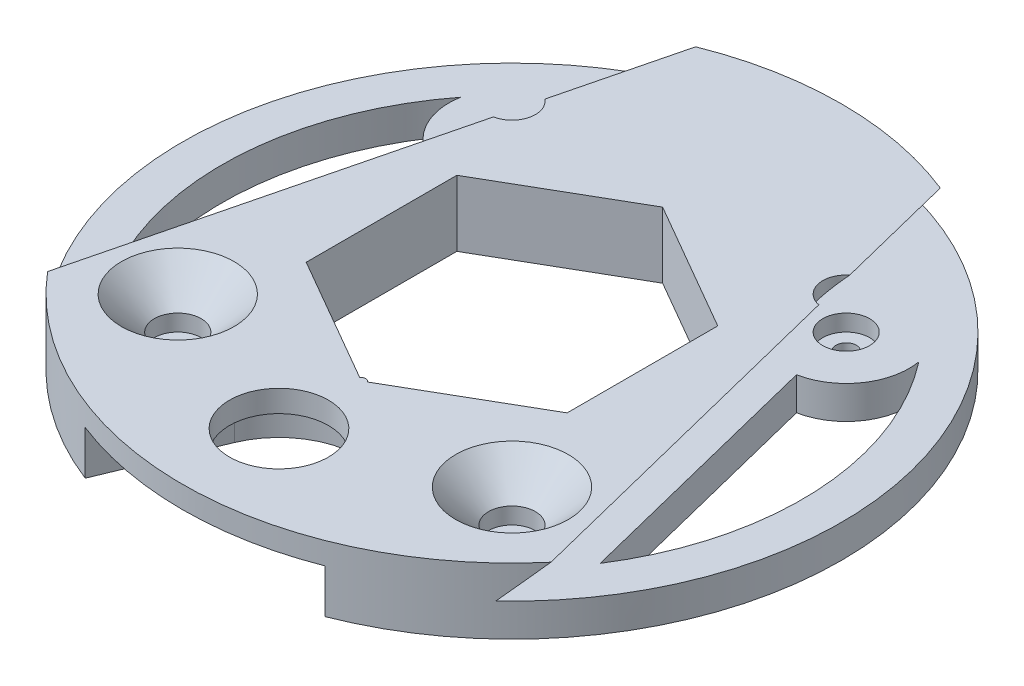
SolidWorks part; units mm, degrees
note: The reader was unsure of these and kept them because the rebuilt part matched: shared geometry of "Sketch1<6>", "Sketch5<3>".
ref_plane "Front Plane" through (0, 0, 0) normal (0, 0, 1) x (1, 0, 0)
ref_plane "Top Plane" through (0, 0, 0) normal (0, 1, 0) x (1, 0, 0)
ref_plane "Right Plane" through (0, 0, 0) normal (1, 0, 0) x (0, 0, -1)
sketch "Sketch1" plane through (0, 0, 0) normal (0, 1, 0) x (1, 0, 0)
  line L0 (-35.3553, -35.3553) -> (-12.941, 48.2963) construction
  line L1 (-34.1053, -36.5626) -> (34.1053, -36.5626) construction
  line L2 (-34.1053, -36.5626) -> (-34.1053, 36.5626) construction
  line L3 (-34.1053, 36.5626) -> (34.1053, 36.5626) construction
  line L4 (34.1053, -36.5626) -> (34.1053, 36.5626) construction
  line L5 (-34.1053, -36.5626) -> (34.1053, 36.5626) construction
  line L6 (-34.1053, 36.5626) -> (34.1053, -36.5626) construction
  line L7 (0, 96.5926) -> (0, -94.4212) construction
  line L8 (-34.1053, -36.5626) -> (-11.2548, 48.7168) construction
  line L9 (-35.3553, -35.3553) -> (35.3553, -35.3553) construction
  line L10 (-34.1053, -36.5626) -> (-12.941, 48.2963)
  line L11 (34.1053, -36.5626) -> (12.941, 48.2963)
  circle A0 centre (0, 0) radius 50
  dimension "D1" = 100
  dimension "D4" = 70.7107
  dimension "D2" = 15
  dimension "D3" = 68.2107
  dimension "D5" = 15
extrude "Boss-Extrude1" add sketch "Sketch1" against normal blind 5 contours A0
extrude "Boss-Extrude3" add sketch "Sketch1<6>" along normal blind 5
sketch "Sketch1<6>" plane through (0, 0, 0) normal (0, 1, 0) x (1, 0, 0) same geometry as "Sketch1"
draft "Draft2" type of draft neutral plane draft angle 45 faces to draft 2 face at (23.5231, 2.5, -5.8668) face at (-23.5231, 2.5, -5.8668) neutral plane through (0, 0, 0) neutral plane normal (0, 1, 0) reverse direction yes parameters "D1"=45
sketch "Sketch3" plane through (0, -5, 0) normal (0, -1, 0) x (1, 0, 0)
  line L1 (-35.3553, -35.3553) -> (35.3553, -35.3553) construction
  line L2 (-35.3553, -35.3553) -> (-35.3553, 35.3553) construction
  line L3 (-35.3553, 35.3553) -> (35.3553, 35.3553) construction
  line L4 (35.3553, -35.3553) -> (35.3553, 35.3553) construction
  line L5 (-35.3553, -35.3553) -> (35.3553, 35.3553) construction
  line L6 (-35.3553, 35.3553) -> (35.3553, -35.3553) construction
  circle A0 centre (0, 0) radius 50 construction
  circle A2 centre (0, 35.3553) radius 7.5
  point P0 (0, 0)
  dimension "D1" = 15
extrude "Cut-Extrude3" cut sketch "Sketch3" against normal through all both
sketch "Sketch4" plane through (0, -5, 0) normal (0, -1, 0) x (1, 0, 0)
  line L0 (0, 2.6913) -> (23.313, 58.9739)
  line L1 (-23.313, 58.9739) -> (0, 2.6913)
  line L2 (0, 25.3553) -> (0, 59.4863) construction
  circle A1 centre (0, 0) radius 50
  circle A2 centre (0, 0) radius 50
  circle A6 centre (0, 35.3553) radius 12.5
  circle A7 centre (0, 35.3553) radius 12.5
  circle M5 centre (0, 35.3553) radius 7.5
  circle M6 centre (0, 0) radius 50
  dimension "D2" = 5
  dimension "D3" = 45
  dimension "D1" = 0
extrude "Cut-Extrude5" cut sketch "Sketch4" against normal blind 6.6667 contours L2 A7 M5 | A7 L2 M5 | L2 A7 L0 M6 | A7 L2 A2 L1
sketch "Sketch5" plane through (0, -5, 0) normal (0, -1, 0) x (1, 0, 0)
  line L0 (-25.3553, 25.3553) -> (25.3553, 25.3553) construction
  line L1 (-35.3553, -35.3553) -> (35.3553, -35.3553) construction
  line L2 (-35.3553, -35.3553) -> (-35.3553, 35.3553) construction
  line L3 (-35.3553, 35.3553) -> (35.3553, 35.3553) construction
  line L4 (35.3553, -35.3553) -> (35.3553, 35.3553) construction
  line L5 (-35.3553, -35.3553) -> (35.3553, 35.3553) construction
  line L6 (-35.3553, 35.3553) -> (35.3553, -35.3553) construction
  line L7 (25.3553, -25.3553) -> (25.3553, 25.3553) construction
  line L8 (-25.3553, -25.3553) -> (25.3553, -25.3553) construction
  line L9 (-25.3553, -25.3553) -> (-25.3553, 25.3553) construction
  line L12 (0, -5.5) -> (0, 5.5) construction
  line L13 (5.5, 0) -> (-5.5, 0) construction
  arc A0 (-18.1786, 46.5783) -> (18.1786, 46.5783) centre (0, 0) ccw construction
  circle A1 centre (-25.3553, 25.3553) radius 1.55
  circle A4 centre (-25.3553, 25.3553) radius 3.55
  circle A5 centre (25.3553, 25.3553) radius 1.55
  circle A6 centre (25.3553, 25.3553) radius 3.55
  circle A7 centre (25.3553, -25.3553) radius 1.55
  circle A8 centre (25.3553, -25.3553) radius 3.55
  circle A9 centre (-25.3553, -25.3553) radius 1.55
  circle A10 centre (-25.3553, -25.3553) radius 3.55
  point P0 (0, 0)
  dimension "D3" = 3.1
  dimension "D2" = 10
  dimension "D1" = 10
  dimension "D4" = 2
extrude "Cut-Extrude6" cut sketch "Sketch5" against normal through all contours A6 A5 | A5 | A8 A7 | A7 | A9 | A10 A9 | A4 A1 | A1
extrude "Boss-Extrude4" add sketch "Sketch5<3>" against normal blind 2.5 contours A8 A7 | A10 A9 | A6 A5 | A4 A1
sketch "Sketch5<3>" plane through (0, -5, 0) normal (0, -1, 0) x (1, 0, 0) same geometry as "Sketch5"
sketch "Sketch6" plane through (0, 5, 0) normal (0, 1, 0) x (1, 0, 0)
  line L1 (0, -22.8553) -> (19.7933, -11.4277)
  line L2 (19.7933, -11.4277) -> (19.7933, 11.4277)
  line L3 (19.7933, 11.4277) -> (0, 22.8553)
  line L4 (0, 22.8553) -> (-19.7933, 11.4277)
  line L5 (-19.7933, 11.4277) -> (-19.7933, -11.4277)
  line L6 (-19.7933, -11.4277) -> (0, -22.8553)
  arc A0 (11.5485, -30.5718) -> (-11.5485, -30.5718) centre (0, -35.3553) ccw construction
  arc A1 (11.5485, -30.5718) -> (-11.5485, -30.5718) centre (0, -35.3553) ccw
  circle A2 centre (0, 0) radius 19.7933 construction
  circle A3 centre (0, -22.8553) radius 0.6639
extrude "Cut-Extrude8" cut sketch "Sketch6" against normal through all contours A3 L1 L2 L3 L4 L5 L6
chamfer "Chamfer1" distance 5 angle 45 2 edges at (25.3553, 5, 21.8053) (-25.3553, 5, 21.8053)
sketch "Sketch7" plane through (0, 0, 0) normal (0, 1, 0) x (1, 0, 0)
  line L0 (-37.0785, -23.6894) -> (-21.6112, 38.327)
  line L1 (-34.1053, -36.5626) -> (-12.941, 48.2963)
  line L2 (-34.1053, -36.5626) -> (-12.941, 48.2963)
  arc A0 (-21.6112, 38.327) -> (-37.0785, -23.6894) centre (0, 0) ccw
  arc A1 (-12.941, 48.2963) -> (-34.1053, -36.5626) centre (0, 0) ccw
  arc A2 (-12.941, 48.2963) -> (-34.1053, -36.5626) centre (0, 0) ccw
  circle A3 centre (-25.3553, 25.3553) radius 3.55 construction
  circle A4 centre (-25.3553, 25.3553) radius 3.55
  circle A5 centre (-25.3553, 25.3553) radius 9.55
  dimension "D1" = 0
  dimension "D2" = 6
  dimension "D3" = 6
extrude "Cut-Extrude9" cut sketch "Sketch7" against normal through all both contours A5 A0 L0
mirror "Mirror1" about plane through (0, 0, 0) normal (1, 0, 0) of "Cut-Extrude9"
